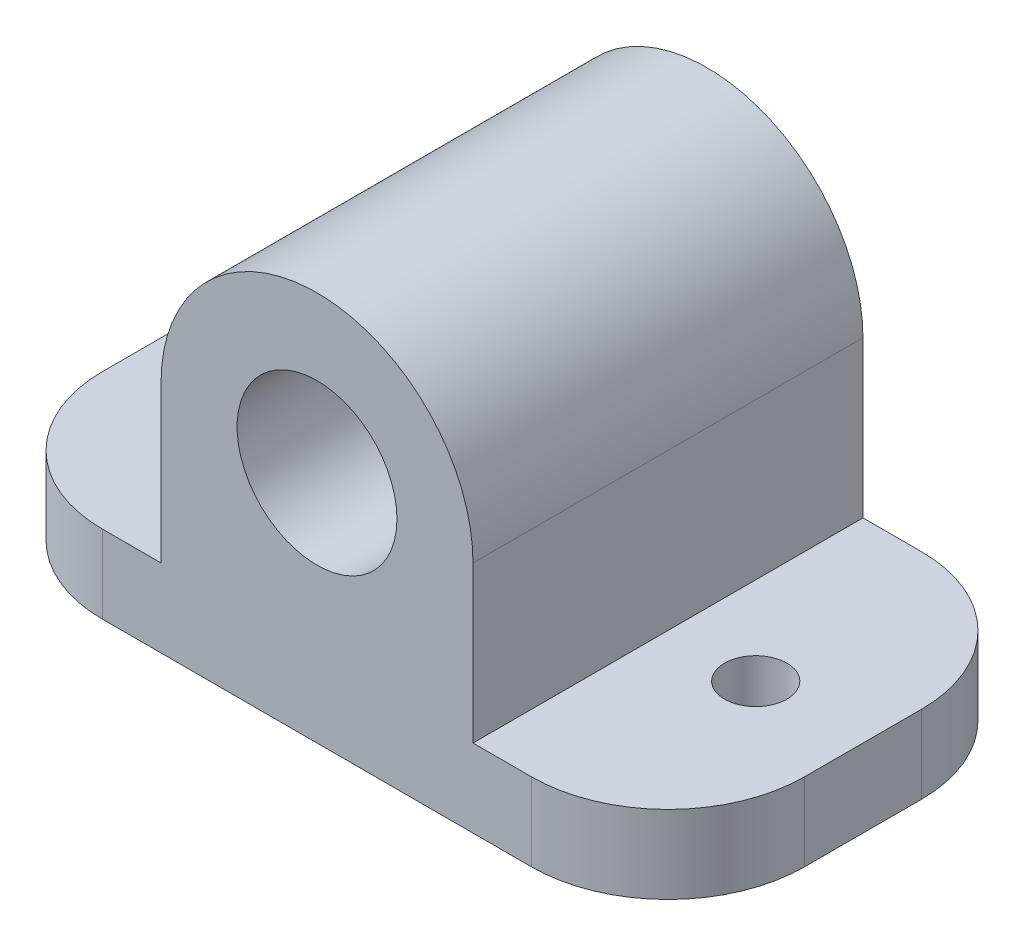
SolidWorks part; units mm, degrees
material "ABS"
ref_plane "Plano frontal" through (0, 0, 0) normal (0, 0, 1) x (1, 0, 0)
ref_plane "Plano superior" through (0, 0, 0) normal (0, 1, 0) x (1, 0, 0)
ref_plane "Plano direito" through (0, 0, 0) normal (1, 0, 0) x (0, 0, -1)
sketch "Esboço1" plane through (0, 0, 0) normal (0, 0, 1) x (1, 0, 0)
  line L0 (-8, 0) -> (-8, -8)
  line L1 (-8, -8) -> (-18, -8)
  line L2 (-18, -8) -> (-18, -12)
  line L3 (-18, -12) -> (18, -12)
  line L4 (0, 8) -> (0, -12) construction
  line L5 (18, -8) -> (18, -12)
  line L6 (8, -8) -> (18, -8)
  line L7 (8, 0) -> (8, -8)
  circle A0 centre (0, 0) radius 4.1
  arc A1 (8, 0) -> (-8, 0) centre (0, 0) ccw
  dimension "D1" = 8.2
  dimension "D2" = 8
  dimension "D3" = 10
  dimension "D4" = 4
extrude "Ressalto-extrusão1" add sketch "Esboço1" along normal blind 20
sketch "Esboço2" plane through (0, -8, 0) normal (0, 1, 0) x (1, 0, 0)
  line L0 (0, 0) -> (0, -20) construction
  line L1 (-8, -20) -> (8, -20) construction
  line L2 (-18, -20) -> (-18, 0) construction
  circle A0 centre (-12.5, -10) radius 1.6
  circle A1 centre (12.5, -10) radius 1.6
  point P12 (-18, -10)
  dimension "D2" = 3.2
  dimension "D1" = 25
extrude "Corte-extrusão1" cut sketch "Esboço2" against normal blind 20
fillet "Filete1" radius 7 4 edges at (-18, -10, 0) (-18, -10, 20) (18, -10, 20) (18, -10, 0)
